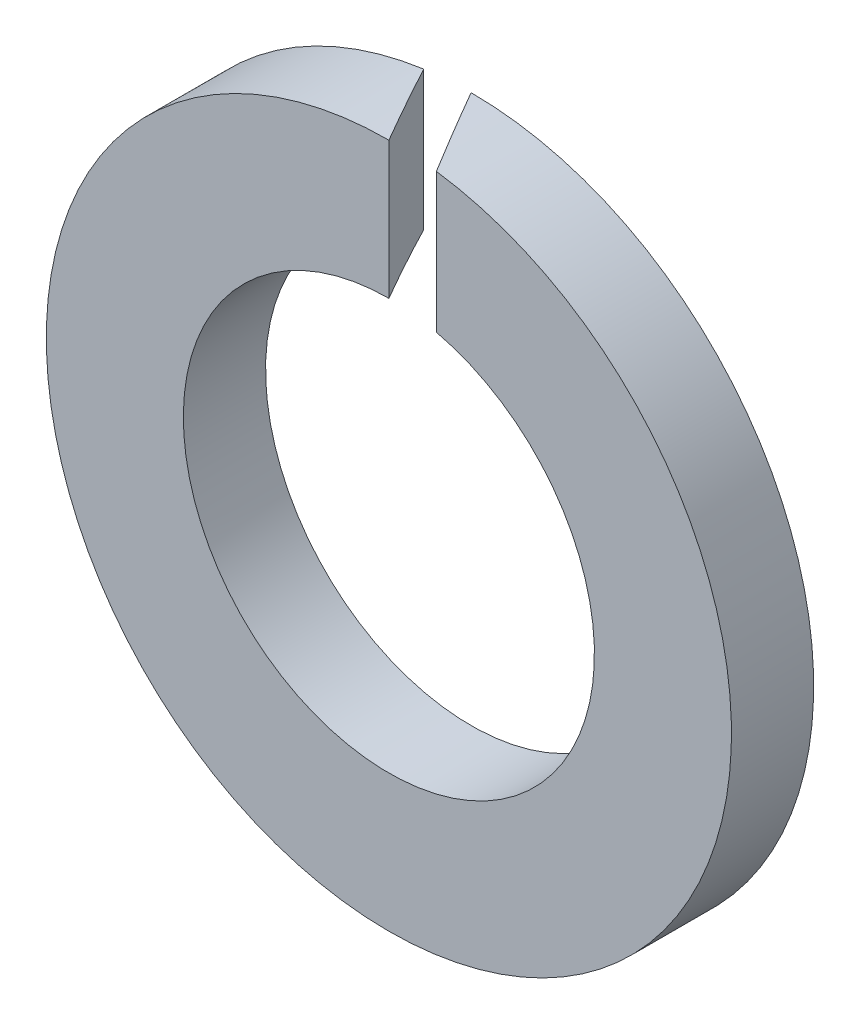
SolidWorks part; units mm, degrees
ref_plane "Front" through (0, 0, 0) normal (0, 0, 1) x (1, 0, 0)
ref_plane "Top" through (0, 0, 0) normal (0, 1, 0) x (1, 0, 0)
ref_plane "Right" through (0, 0, 0) normal (1, 0, 0) x (0, 0, -1)
sketch "Sketch1" plane through (0, 0, 0) normal (0, 0, 1) x (1, 0, 0)
  circle A0 centre (0, 0) radius 1.5
  circle A1 centre (0, 0) radius 2.5
  dimension "d" = 3
  dimension "b" = 1
extrude "Base-Extrude" add sketch "Sketch1" against normal blind 0.6
sketch "Sketch2" plane through (0, 0, 0) normal (0, 1, 0) x (1, 0, 0)
  line L0 (0, 0.6) -> (0.3464, 0)
  line L1 (0.3464, 0) -> (0, 0)
  line L3 (0, 0) -> (-0.3464, 0.6)
  line L5 (-0.3464, 0.6) -> (0, 0.6)
  line L7 (2.5, 0.6) -> (-2.5, 0.6) construction
  dimension "m" = 0.3
extrude "Cut-Extrude1" cut sketch "Sketch2" along normal through all
